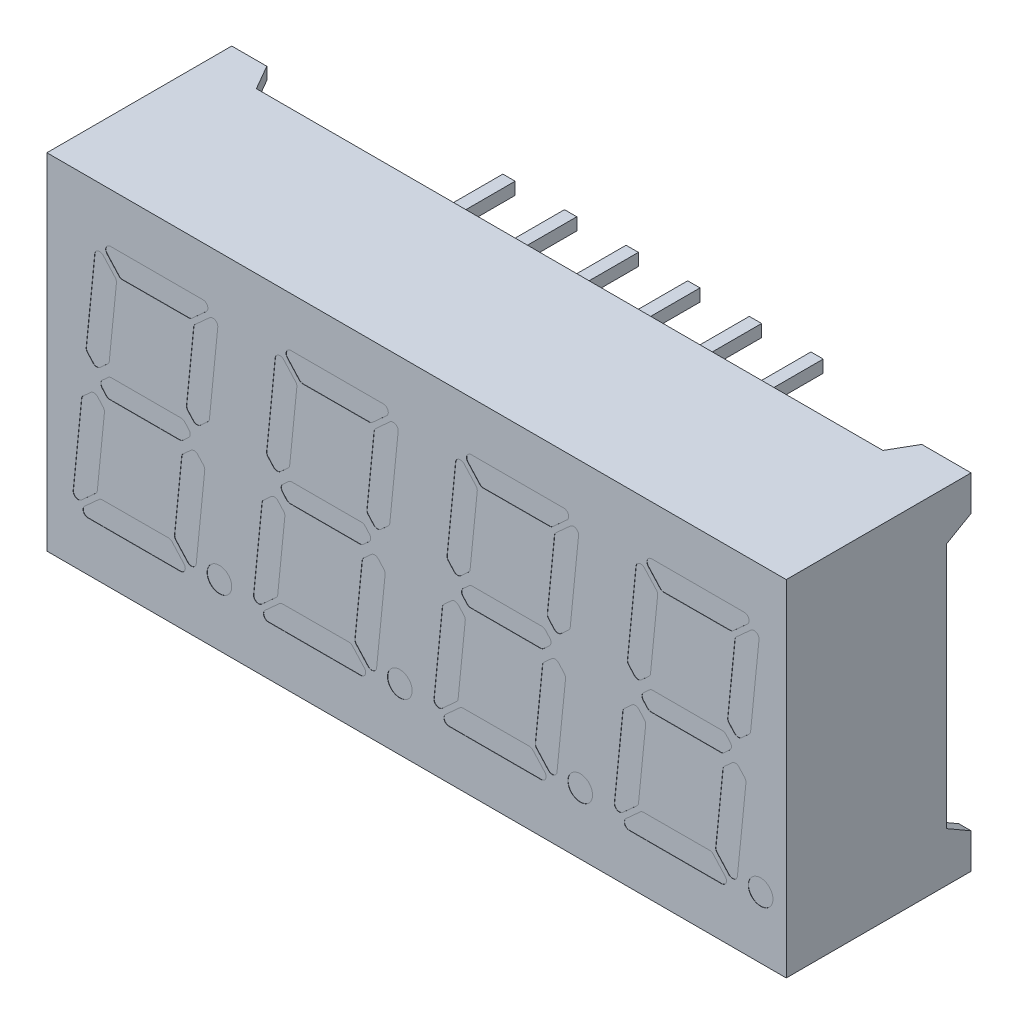
SolidWorks part; units mm, degrees
material "ABS"
ref_plane "Спереди" through (0, 0, 0) normal (0, 0, 1) x (1, 0, 0)
ref_plane "Сверху" through (0, 0, 0) normal (0, 1, 0) x (1, 0, 0)
ref_plane "Справа" through (0, 0, 0) normal (1, 0, 0) x (0, 0, -1)
sketch "Эскиз1" plane through (0, 0, 0) normal (0, 0, 1) x (1, 0, 0)
  line L1 (15, -7) -> (-15, -7)
  line L2 (15, -7) -> (15, 7)
  line L3 (15, 7) -> (-15, 7)
  line L4 (-15, -7) -> (-15, 7)
  line L5 (15, -7) -> (-15, 7) construction
  line L6 (15, 7) -> (-15, -7) construction
  point P0 (0, 0)
  dimension "D1" = 14
  dimension "D2" = 30
extrude "Бобышка-Вытянуть1" add sketch "Эскиз1" along normal blind 7.5 contours L3 L4 L1 L2
sketch "Эскиз2" plane through (0, 0, 0) normal (0, 0, -1) x (-1, 0, 0)
  line L0 (-15, -7) -> (-15, 7) construction
  line L1 (13, -5) -> (-13, -5) construction
  line L2 (13, -5) -> (13, 5) construction
  line L3 (13, 5) -> (-13, 5) construction
  line L4 (-13, -5) -> (-13, 5) construction
  line L5 (13, -5) -> (-13, 5) construction
  line L6 (13, 5) -> (-13, -5) construction
  line L7 (-15, 7) -> (15, 7) construction
  line L9 (13, -11.5254) -> (-13, -11.5254)
  line L10 (13, -11.5254) -> (13, 11.5254)
  line L11 (13, 11.5254) -> (-13, 11.5254)
  line L12 (-13, -11.5254) -> (-13, 11.5254)
  line L13 (13, -11.5254) -> (-13, 11.5254) construction
  line L14 (13, 11.5254) -> (-13, -11.5254) construction
  line L15 (24.1401, -5) -> (-24.1401, -5)
  line L16 (24.1401, -5) -> (24.1401, 5)
  line L17 (24.1401, 5) -> (-24.1401, 5)
  line L18 (-24.1401, -5) -> (-24.1401, 5)
  line L19 (24.1401, -5) -> (-24.1401, 5) construction
  line L20 (24.1401, 5) -> (-24.1401, -5) construction
  point P0 (0, 0)
  point P10 (0, 0)
  point P15 (0, 0)
  line M13 (-15, 7) -> (-15, -7)
  line M14 (-15, -7) -> (15, -7)
  line M15 (15, -7) -> (15, 7)
  line M16 (15, 7) -> (-15, 7)
  dimension "D1" = 2
  dimension "D2" = 2
  dimension "D3" = 23.0507
  dimension "D4" = 48.2801
extrude "Вырез-Вытянуть1" cut sketch "Эскиз2" against normal blind 1 contours L18 L15 L17 M13 | L12 L17 L15 M13 | L10 L17 L12 L15 | L17 L10 L12 M16 | L10 L15 L12 M14 | L17 L10 L15 M15 | L16 L17 L15 M15 | L12 L10 L11 M16 | L12 L9 L10 M14 region at (0, -9.2627, 0) region at (0, -6, 0) region at (0, 0, 0) region at (-14, 0, 0) region at (14, 0, 0) region at (0, 6, 0) region at (-19.57, 0, 0) region at (19.57, 0, 0) region at (0, 9.2627, 0)
shell "Оболочка1" thickness 0.5 removed face at (-13, 6, 0.5) removed face at (-14, 6, 0) removed face at (-14, 5, 0.5) removed face at (-14, -5, 0.5) removed face at (-14, -6, 0) removed face at (-13, -6, 0.5) removed face at (14, -5, 0.5) removed face at (13, 6, 0.5) removed face at (14, 5, 0.5) removed face at (14, 6, 0) removed face at (13, -6, 0.5) removed face at (14, -6, 0)
sketch "Эскиз3" plane through (0, 0, 7) normal (0, 0, -1) x (-1, 0, 0)
  line L4 (-13, -6.5) -> (-13, -5)
  line L5 (-13, -5) -> (-14.5, -5)
  line L6 (-14.5, -5) -> (-14.5, -6.5)
  line L7 (-14.5, -6.5) -> (-13, -6.5)
  line L8 (-13, -6.5) -> (-13, -5)
  line L9 (-13, -5) -> (-14.5, -5)
  line L10 (-14.5, -5) -> (-14.5, -6.5)
  line L11 (-14.5, -6.5) -> (-13, -6.5)
  line L12 (-13, 5) -> (-13, 6.5)
  line L13 (-13, 6.5) -> (-14.5, 6.5)
  line L14 (-14.5, 6.5) -> (-14.5, 5)
  line L15 (-14.5, 5) -> (-13, 5)
  line L16 (-13, 5) -> (-13, 6.5)
  line L17 (-13, 6.5) -> (-14.5, 6.5)
  line L18 (-14.5, 6.5) -> (-14.5, 5)
  line L19 (-14.5, 5) -> (-13, 5)
  line L20 (13, 5) -> (14.5, 5)
  line L21 (14.5, 5) -> (14.5, 6.5)
  line L22 (14.5, 6.5) -> (13, 6.5)
  line L23 (13, 6.5) -> (13, 5)
  line L24 (13, 5) -> (14.5, 5)
  line L25 (14.5, 5) -> (14.5, 6.5)
  line L26 (14.5, 6.5) -> (13, 6.5)
  line L27 (13, 6.5) -> (13, 5)
  line L28 (14.5, -5) -> (13, -5)
  line L29 (13, -5) -> (13, -6.5)
  line L30 (13, -6.5) -> (14.5, -6.5)
  line L31 (14.5, -6.5) -> (14.5, -5)
  line L32 (14.5, -5) -> (13, -5)
  line L33 (13, -5) -> (13, -6.5)
  line L34 (13, -6.5) -> (14.5, -6.5)
  line L35 (14.5, -6.5) -> (14.5, -5)
  dimension "D1" = 0
  dimension "D2" = 0
  dimension "D3" = 0
  dimension "D4" = 0
extrude "Бобышка-Вытянуть2" add sketch "Эскиз3" along normal up to surface (6 mm away) up to face at (0, 0, 1)
chamfer "Фаска1" distance 1 angle 30 5 edges at (-13, 6.75, 0) (-14.75, -5, 0) (13, -6.75, 0) (14.75, 5, 0) (13, 6.75, 1) first distance on face at (-13, 6.75, 0.5) first distance on face at (-14.75, -5, 0.5) first distance on face at (13, -6.75, 0.5) first distance on face at (14.75, 5, 0.5) first distance on face at (13, 6.75, 0.5)
chamfer "Фаска2" distance 1 angle 30 3 edges at (14.75, -5, 0) (-13, -6.75, 0) (-14.75, 5, 0) first distance on face at (14.75, -5, 0.5) first distance on face at (-13, -6.75, 0.5) first distance on face at (-14.75, 5, 0.5)
sketch "Эскиз5" plane through (0, 0, 1) normal (0, 0, -1) x (-1, 0, 0)
  line L0 (-12.4226, 6.5) -> (13, 6.5)
  line L1 (14.5, 5) -> (14.5, -5)
  line L2 (13, -6.5) -> (-13, -6.5)
  line L3 (-14.5, -5) -> (-14.5, 5)
  line L20 (13, 7) -> (-12.4226, 7)
  line L21 (-12.4226, 7) -> (-12.4226, 6.5)
  line L22 (-12.4226, 6.5) -> (-14.5, 6.5)
  line L23 (-14.5, 6.5) -> (-14.5, 5)
  line L24 (-14.5, 5) -> (-15, 5)
  line L25 (-15, 5) -> (-15, -5)
  line L26 (-15, -5) -> (-14.5, -5)
  line L27 (-14.5, -5) -> (-14.5, -6.5)
  line L28 (-14.5, -6.5) -> (-13, -6.5)
  line L29 (-13, -6.5) -> (-13, -7)
  line L30 (-13, -7) -> (13, -7)
  line L31 (13, -7) -> (13, -6.5)
  line L32 (13, -6.5) -> (14.5, -6.5)
  line L33 (14.5, -6.5) -> (14.5, -5)
  line L34 (14.5, -5) -> (15, -5)
  line L35 (15, -5) -> (15, 5)
  line L36 (15, 5) -> (14.5, 5)
  line L37 (14.5, 5) -> (14.5, 6.5)
  line L38 (14.5, 6.5) -> (13, 6.5)
  line L39 (13, 6.5) -> (13, 7)
  line L40 (13, 7) -> (-12.4226, 7)
  line L41 (-12.4226, 7) -> (-12.4226, 6.5)
  line L42 (-12.4226, 6.5) -> (-14.5, 6.5)
  line L43 (-14.5, 6.5) -> (-14.5, 5)
  line L44 (-14.5, 5) -> (-15, 5)
  line L45 (-15, 5) -> (-15, -5)
  line L46 (-15, -5) -> (-14.5, -5)
  line L47 (-14.5, -5) -> (-14.5, -6.5)
  line L48 (-14.5, -6.5) -> (-13, -6.5)
  line L49 (-13, -6.5) -> (-13, -7)
  line L50 (-13, -7) -> (13, -7)
  line L51 (13, -7) -> (13, -6.5)
  line L52 (13, -6.5) -> (14.5, -6.5)
  line L53 (14.5, -6.5) -> (14.5, -5)
  line L54 (14.5, -5) -> (15, -5)
  line L55 (15, -5) -> (15, 5)
  line L56 (15, 5) -> (14.5, 5)
  line L57 (14.5, 5) -> (14.5, 6.5)
  line L58 (14.5, 6.5) -> (13, 6.5)
  line L59 (13, 6.5) -> (13, 7)
  line M23 (-12.4226, 6.5) -> (-14.5, 6.5)
  line M24 (-14.5, 6.5) -> (-14.5, 5)
  line M28 (-14.5, -5) -> (-14.5, -6.5)
  line M29 (-14.5, -6.5) -> (-13, -6.5)
  line M33 (13, -6.5) -> (14.5, -6.5)
  line M34 (14.5, -6.5) -> (14.5, -5)
  line M38 (14.5, 5) -> (14.5, 6.5)
  line M39 (14.5, 6.5) -> (13, 6.5)
  dimension "D1" = 0
extrude "Вырез-Вытянуть2" cut sketch "Эскиз5" against normal blind 1 contours L3 L2 L1 L0 M28 M29 M33 M34 M38 M39 M23 M24 region at (0, 0, 1)
sketch "Эскиз4" plane through (0, 0, 2) normal (0, 0, -1) x (-1, 0, 0)
  line L0 (0, 0) -> (0, 10.0588) construction
  line L5 (13, 7) -> (-12.4226, 7) construction
  line L6 (-1, 5) -> (-1.5, 5)
  line L7 (-1, 5) -> (-1, 5.5)
  line L8 (-1, 5.5) -> (-1.5, 5.5)
  line L9 (-1.5, 5) -> (-1.5, 5.5)
  line L10 (-1, 5) -> (-1.5, 5.5) construction
  line L11 (-1, 5.5) -> (-1.5, 5) construction
  line L12 (1.5, 5) -> (1.5, 5.5)
  line L13 (1.5, 5) -> (1, 5)
  line L14 (1, 5) -> (1, 5.5)
  line L15 (1.5, 5.5) -> (1, 5.5)
  line L16 (4, 5) -> (4, 5.5)
  line L17 (4, 5) -> (3.5, 5)
  line L18 (3.5, 5) -> (3.5, 5.5)
  line L19 (4, 5.5) -> (3.5, 5.5)
  line L20 (6.5, 5) -> (6.5, 5.5)
  line L21 (6.5, 5) -> (6, 5)
  line L22 (6, 5) -> (6, 5.5)
  line L23 (6.5, 5.5) -> (6, 5.5)
  line L24 (-1, 5) -> (-1, 5.5)
  line L25 (-1, 5) -> (-1.5, 5)
  line L26 (-1.5, 5) -> (-1.5, 5.5)
  line L27 (-1, 5.5) -> (-1.5, 5.5)
  line L28 (1.5, 5) -> (1.5, 5.5)
  line L29 (1.5, 5) -> (1, 5)
  line L30 (1, 5) -> (1, 5.5)
  line L31 (1.5, 5.5) -> (1, 5.5)
  line L32 (4, 5) -> (4, 5.5)
  line L33 (4, 5) -> (3.5, 5)
  line L34 (3.5, 5) -> (3.5, 5.5)
  line L35 (4, 5.5) -> (3.5, 5.5)
  line L36 (-3.5, 5) -> (-3.5, 5.5)
  line L37 (-3.5, 5) -> (-4, 5)
  line L38 (-4, 5) -> (-4, 5.5)
  line L39 (-3.5, 5.5) -> (-4, 5.5)
  line L40 (-1, 5) -> (-1, 5.5)
  line L41 (-1, 5) -> (-1.5, 5)
  line L42 (-1.5, 5) -> (-1.5, 5.5)
  line L43 (-1, 5.5) -> (-1.5, 5.5)
  line L44 (1.5, 5) -> (1.5, 5.5)
  line L45 (1.5, 5) -> (1, 5)
  line L46 (1, 5) -> (1, 5.5)
  line L47 (1.5, 5.5) -> (1, 5.5)
  line L48 (-3.5, 5) -> (-3.5, 5.5)
  line L49 (-3.5, 5) -> (-4, 5)
  line L50 (-4, 5) -> (-4, 5.5)
  line L51 (-3.5, 5.5) -> (-4, 5.5)
  line L52 (-6, 5) -> (-6, 5.5)
  line L53 (-6, 5) -> (-6.5, 5)
  line L54 (-6.5, 5) -> (-6.5, 5.5)
  line L55 (-6, 5.5) -> (-6.5, 5.5)
  line L56 (0, 0) -> (-6, 0) construction
  line L57 (-1, -5.5) -> (-1.5, -5) construction
  line L58 (-1, -5) -> (-1.5, -5.5) construction
  line L59 (-6, -5.5) -> (-6.5, -5.5)
  line L60 (-6.5, -5) -> (-6.5, -5.5)
  line L61 (-6, -5) -> (-6.5, -5)
  line L62 (-6, -5) -> (-6, -5.5)
  line L63 (-3.5, -5.5) -> (-4, -5.5)
  line L64 (-4, -5) -> (-4, -5.5)
  line L65 (-3.5, -5) -> (-4, -5)
  line L66 (-3.5, -5) -> (-3.5, -5.5)
  line L67 (1.5, -5.5) -> (1, -5.5)
  line L68 (1, -5) -> (1, -5.5)
  line L69 (1.5, -5) -> (1, -5)
  line L70 (1.5, -5) -> (1.5, -5.5)
  line L71 (-1, -5.5) -> (-1.5, -5.5)
  line L72 (-1.5, -5) -> (-1.5, -5.5)
  line L73 (-1, -5) -> (-1.5, -5)
  line L74 (-1, -5) -> (-1, -5.5)
  line L75 (-3.5, -5.5) -> (-4, -5.5)
  line L76 (-4, -5) -> (-4, -5.5)
  line L77 (-3.5, -5) -> (-4, -5)
  line L78 (-3.5, -5) -> (-3.5, -5.5)
  line L79 (4, -5.5) -> (3.5, -5.5)
  line L80 (3.5, -5) -> (3.5, -5.5)
  line L81 (4, -5) -> (3.5, -5)
  line L82 (4, -5) -> (4, -5.5)
  line L83 (1.5, -5.5) -> (1, -5.5)
  line L84 (1, -5) -> (1, -5.5)
  line L85 (1.5, -5) -> (1, -5)
  line L86 (1.5, -5) -> (1.5, -5.5)
  line L87 (-1, -5.5) -> (-1.5, -5.5)
  line L88 (-1.5, -5) -> (-1.5, -5.5)
  line L89 (-1, -5) -> (-1.5, -5)
  line L90 (-1, -5) -> (-1, -5.5)
  line L91 (6.5, -5.5) -> (6, -5.5)
  line L92 (6, -5) -> (6, -5.5)
  line L93 (6.5, -5) -> (6, -5)
  line L94 (6.5, -5) -> (6.5, -5.5)
  line L95 (4, -5.5) -> (3.5, -5.5)
  line L96 (3.5, -5) -> (3.5, -5.5)
  line L97 (4, -5) -> (3.5, -5)
  line L98 (4, -5) -> (4, -5.5)
  line L99 (1.5, -5.5) -> (1, -5.5)
  line L100 (1, -5) -> (1, -5.5)
  line L101 (1.5, -5) -> (1, -5)
  line L102 (1.5, -5) -> (1.5, -5.5)
  line L103 (-1.5, -5) -> (-1.5, -5.5)
  line L104 (-1, -5.5) -> (-1.5, -5.5)
  line L105 (-1, -5) -> (-1, -5.5)
  line L106 (-1, -5) -> (-1.5, -5)
  point P2 (-1.25, 5.25)
  point P79 (-1.25, -5.25)
  dimension "D1" = 0.5
  dimension "D2" = 1.5
  dimension "D3" = 2
  dimension "D6" = 2
  dimension "D7" = 2
  dimension "D4" = 4
  dimension "D5" = 3
extrude "Бобышка-Вытянуть3" add sketch "Эскиз4" along normal blind 4.5 contours L62 L61 L60 L59 | L66 L65 L64 L63 | L74 L73 L72 L71 | L70 L69 L68 L67 | L82 L81 L80 L79 | L94 L93 L92 L91 | L16 L19 L18 L17 | L12 L15 L14 L13 | L9 L6 L7 L8 | L36 L39 L38 L37 | L52 L55 L54 L53 | L22 L23 L20 L21 region at (1.25, 5.25, 2) region at (-1.25, 5.25, 2) region at (-3.75, 5.25, 2) region at (3.75, 5.25, 2) region at (6.25, 5.25, 2) region at (6.25, -5.25, 2) region at (3.75, -5.25, 2) region at (-1.25, -5.25, 2) region at (1.25, -5.25, 2) region at (-3.75, -5.25, 2) region at (-6.25, -5.25, 2)
sketch "Эскиз6" plane through (0, 0, 7.5) normal (0, 0, 1) x (1, 0, 0)
  line L0 (0, 0) -> (0, 9.0067) construction
  line L1 (-14, -5) -> (-9, -5)
  line L2 (-14, -5) -> (-13, 5)
  line L3 (-9, -5) -> (-8, 5)
  line L4 (-13, 5) -> (-8, 5)
  line L5 (-15, -7) -> (-15, 7) construction
  line L6 (-14, -5) -> (-8, 5) construction
  line L7 (-13, 5) -> (-9, -5) construction
  line L8 (-13, 4) -> (-8, 4) construction
  line L9 (-13.005, -5.0995) -> (-12.005, 4.9005) construction
  line L10 (-9.995, -4.9005) -> (-8.995, 5.0995) construction
  line L11 (-14, -4) -> (-9, -4) construction
  line L12 (-13.1, 4) -> (-8.1, 4)
  line L13 (-13.9, -4) -> (-8.9, -4)
  line L14 (-9.005, 5) -> (-10.005, -5)
  line L15 (-11.995, 5) -> (-12.995, -5)
  line L16 (-13.5, 0) -> (-8.5, 0) construction
  line L17 (-13.5, -0.4) -> (-8.5, -0.4)
  line L18 (-13.5, 0.4) -> (-8.5, 0.4)
  line L19 (-13, 5) -> (-12.095, 4) construction
  line L20 (-8, 5) -> (-9.105, 4) construction
  line L21 (-14, -5) -> (-12.895, -4) construction
  line L22 (-9.905, -4) -> (-9, -5) construction
  line L23 (-13.9329, -5.0741) -> (-12.8279, -4.0741)
  line L24 (-9.9791, -4.0671) -> (-9.0741, -5.0671)
  line L25 (-8.0671, 5.0741) -> (-9.1721, 4.0741)
  line L26 (-13.0741, 4.9329) -> (-12.1692, 3.9329) construction
  line L27 (-14.0671, -4.9259) -> (-12.9621, -3.9259) construction
  line L28 (-9.8308, -3.9329) -> (-8.9259, -4.9329) construction
  line L29 (-7.9329, 4.9259) -> (-9.0379, 3.9259) construction
  line L30 (-12.9259, 5.0671) -> (-12.0209, 4.0671)
  line L31 (-13.0741, 4.9329) -> (-12.1084, 3.8658)
  line L32 (-7.9329, 4.9259) -> (-9.1198, 3.8517)
  line L33 (-8.9259, -4.9329) -> (-9.8916, -3.8658)
  line L34 (-14.0671, -4.9259) -> (-12.8802, -3.8517)
  line L35 (-12.0209, 4.0671) -> (-9.1721, 4.0741)
  line L36 (-9.0379, 3.9259) -> (-9.3442, 0.8629)
  line L37 (-9.3442, 0.8629) -> (-8.9252, 0.4)
  line L38 (-8.9252, 0.4) -> (-8.4137, 0.8629)
  line L39 (-12.8279, -4.0741) -> (-9.9791, -4.0671)
  line L40 (-9.8308, -3.9329) -> (-9.5242, -0.8664)
  line L41 (-9.5242, -0.8664) -> (-9.0088, -0.4)
  line L42 (-9.0088, -0.4) -> (-8.5866, -0.8664)
  line L43 (-12.9621, -3.9259) -> (-12.6558, -0.8629)
  line L44 (-12.6558, -0.8629) -> (-13.0748, -0.4)
  line L45 (-13.0748, -0.4) -> (-13.5863, -0.8629)
  line L46 (-12.1692, 3.9329) -> (-12.4758, 0.8664)
  line L47 (-12.4758, 0.8664) -> (-12.9912, 0.4)
  line L48 (-12.9912, 0.4) -> (-13.4134, 0.8664)
  line L49 (-12.455, 0.4) -> (-12.897, 0)
  line L50 (-12.897, 0) -> (-12.535, -0.4)
  line L51 (-9.465, 0.4) -> (-9.103, 0)
  line L52 (-9.103, 0) -> (-9.545, -0.4)
  line L53 (-8, 5) -> (-8, -4.9329) construction
  circle A0 centre (-8, -4.5) radius 0.5
  point P9 (-11, 0)
  dimension "D11" = 1
  dimension "D1" = 5
  dimension "D2" = 1
  dimension "D3" = 2
  dimension "D4" = 10
  dimension "D5" = 1
  dimension "D6" = 1
  dimension "D7" = 0.4
  dimension "D8" = 0.4
  dimension "D9" = 0.1
  dimension "D10" = 0.1
extrude "Вырез-Вытянуть3" cut sketch "Эскиз6" against normal blind 0.01 contours L30 L35 L25 L14 L4 L15 | L4 L30 L15 | L25 L4 L14 | L3 L32 L12 | L37 L38 L3 L12 L32 L36 | L18 L15 L17 L14 | L52 L51 L14 | L49 L50 L15 | L48 L47 L46 L31 L12 L2 | L31 L2 L12 | L44 L45 L2 L13 L34 L43 | L2 L34 L13 | L23 L1 L15 | L39 L23 L15 L1 L14 L24 | L24 L14 L1 | L33 L3 L13 | L42 L41 L40 L33 L13 L3 | A0 region at (-11.4514, -4.5361, 7.5) region at (-13.2519, -4.7161, 7.5) region at (-9.6861, -4.7114, 7.5) region at (-13.6431, -4.2839, 7.5) region at (-13.2663, -2.3116, 7.5) region at (-9.2189, -4.2886, 7.5) region at (-9.1997, -2.3127, 7.5) region at (-12.629, 0, 7.5) region at (-11, 0, 7.5) region at (-9.371, 0, 7.5) region at (-12.8003, 2.3127, 7.5) region at (-8.7337, 2.3116, 7.5) region at (-12.7811, 4.2886, 7.5) region at (-12.3139, 4.7114, 7.5) region at (-10.5486, 4.5361, 7.5) region at (-8.3569, 4.2839, 7.5) region at (-8.7481, 4.7161, 7.5) region at (-8, -4.5, 7.5)
fillet "Скругление1" radius 0.2 34 edges at (-9.465, 0.4, 7.495) (-12.455, 0.4, 7.495) (-12.897, 0, 7.495) (-12.535, -0.4, 7.495) (-9.545, -0.4, 7.495) (-9.103, 0, 7.495) (-8.0148, 4.8517, 7.495) (-9.0379, 3.9259, 7.495) (-9.3442, 0.8629, 7.495) (-8.9252, 0.4, 7.495) (-8.4137, 0.8629, 7.495) (-8.5866, -0.8664, 7.495) (-9.0088, -0.4, 7.495) (-9.5242, -0.8664, 7.495) (-9.8308, -3.9329, 7.495) (-8.9866, -4.8658, 7.495) (-9.1349, -5, 7.495) (-9.9791, -4.0671, 7.495) (-12.8279, -4.0741, 7.495) (-13.851, -5, 7.495) (-12.9621, -3.9259, 7.495) (-13.9852, -4.8517, 7.495) (-13.5863, -0.8629, 7.495) (-12.6558, -0.8629, 7.495) (-13.0748, -0.4, 7.495) (-13.4134, 0.8664, 7.495) (-12.9912, 0.4, 7.495) (-12.4758, 0.8664, 7.495) (-12.1692, 3.9329, 7.495) (-12.0209, 4.0671, 7.495) (-9.1721, 4.0741, 7.495) (-8.149, 5, 7.495) (-12.8651, 5, 7.495) (-13.0134, 4.8658, 7.495)
pattern_linear "Линейный массив1" count 4 spacing 7.32 along (1, 0, 0) of "Вырез-Вытянуть3", "Скругление1"
